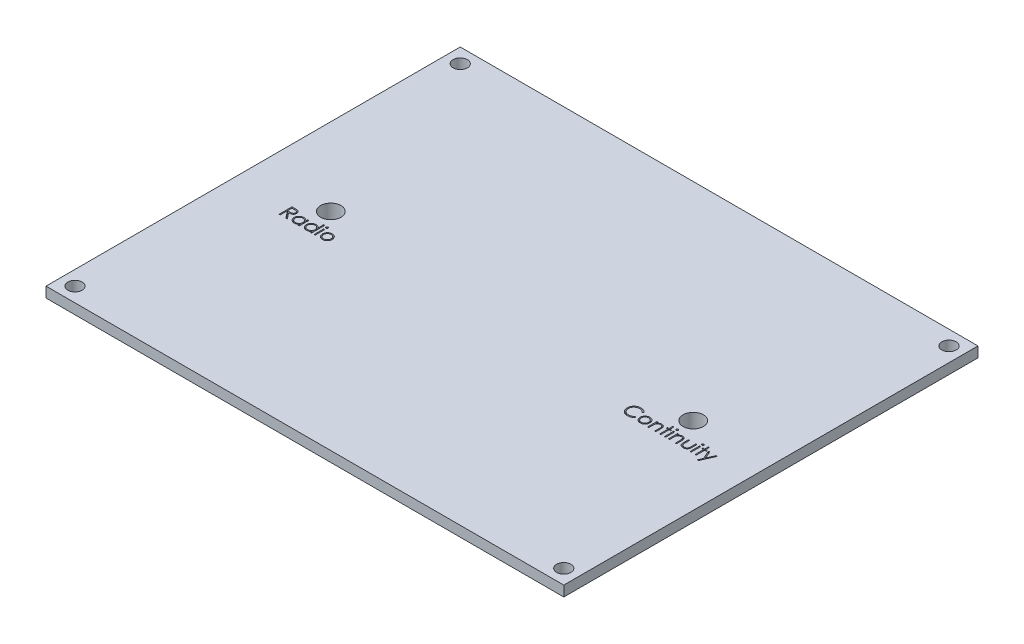
SolidWorks part; units mm, degrees
ref_plane "Front Plane" through (0, 0, 0) normal (0, 0, 1) x (1, 0, 0)
ref_plane "Top Plane" through (0, 0, 0) normal (0, 1, 0) x (1, 0, 0)
ref_plane "Right Plane" through (0, 0, 0) normal (1, 0, 0) x (0, 0, -1)
sketch "Çizim1" plane through (0, 0, 0) normal (0, 1, 0) x (1, 0, 0)
  line L1 (-63.5, 50.8) -> (63.5, 50.8)
  line L2 (-63.5, 50.8) -> (-63.5, -50.8)
  line L3 (-63.5, -50.8) -> (63.5, -50.8)
  line L4 (63.5, 50.8) -> (63.5, -50.8)
  line L5 (-63.5, 50.8) -> (63.5, -50.8) construction
  line L6 (-63.5, -50.8) -> (63.5, 50.8) construction
  point P0 (0, 0)
  dimension "D1" = 127
  dimension "D2" = 101.6
extrude "Yükseklik-Ekstrüzyon1" add sketch "Çizim1" along normal blind 2.54
sketch "Çizim3" plane through (0, 0, 0) normal (0, -1, 0) x (1, 0, 0)
  line L1 (-56.515, 43.815) -> (56.515, 43.815)
  line L2 (-56.515, 43.815) -> (-56.515, -43.815)
  line L3 (-56.515, -43.815) -> (56.515, -43.815)
  line L4 (56.515, 43.815) -> (56.515, -43.815)
  line L5 (-56.515, 43.815) -> (56.515, -43.815) construction
  line L6 (-56.515, -43.815) -> (56.515, 43.815) construction
  point P0 (0, 0)
  dimension "D1" = 113.03
  dimension "D2" = 87.63
extrude "Yükseklik-Ekstrüzyon2" add sketch "Çizim3" along normal blind 1.27 contours L1 L4 L3 L2
sketch "Çizim4" plane through (0, 2.54, 0) normal (0, 1, 0) x (1, 0, 0)
  line L0 (63.5, 50.8) -> (-63.5, 50.8) construction
  line L1 (-63.5, 50.8) -> (-63.5, -50.8) construction
  circle A0 centre (-59.944, 47.244) radius 1.7526
  dimension "D1" = 3.556
  dimension "D2" = 3.556
sketch "Çizim5" plane through (0, 2.54, 0) normal (0, 1, 0) x (1, 0, 0)
  line L0 (63.5, 50.8) -> (-63.5, 50.8) construction
  line L1 (63.5, -50.8) -> (63.5, 50.8) construction
  circle A0 centre (59.944, 47.244) radius 1.7526
  dimension "D1" = 3.556
  dimension "D2" = 3.556
extrude "Kes-Ekstrüzyon1" cut sketch "Çizim4" against normal blind 2.54 contours A0
extrude "Kes-Ekstrüzyon2" cut sketch "Çizim5" against normal blind 2.54 contours A0
sketch "Çizim7" plane through (0, 2.54, 0) normal (0, 1, 0) x (1, 0, 0)
  line L0 (-63.5, 50.8) -> (-63.5, -50.8) construction
  line L1 (-63.5, -50.8) -> (63.5, -50.8) construction
  circle A0 centre (-59.944, -47.244) radius 1.7526
  dimension "D1" = 3.556
  dimension "D2" = 3.556
extrude "Kes-Ekstrüzyon3" cut sketch "Çizim7" against normal blind 2.54
sketch "Çizim9" plane through (0, 2.54, 0) normal (0, 1, 0) x (1, 0, 0)
  line L0 (63.5, -50.8) -> (63.5, 50.8) construction
  line L1 (-63.5, -50.8) -> (63.5, -50.8) construction
  circle A0 centre (59.944, -47.244) radius 1.7526
  dimension "D1" = 3.556
  dimension "D2" = 3.556
extrude "Kes-Ekstrüzyon4" cut sketch "Çizim9" against normal blind 2.54
sketch "Çizim10" plane through (0, 2.54, 0) normal (0, 1, 0) x (1, 0, 0)
  line L1 (-63.5, 50.8) -> (-63.5, -50.8) construction
  circle A1 centre (-44.45, 0) radius 2.5
  dimension "D1" = 19.05
extrude "Kes-Ekstrüzyon5" cut sketch "Çizim10" against normal blind 3.81
sketch "Çizim11" plane through (0, 2.54, 0) normal (0, 1, 0) x (1, 0, 0)
  line L0 (63.5, -50.8) -> (63.5, 50.8) construction
  circle A0 centre (44.45, 0) radius 2.5
  dimension "D1" = 0
  dimension "D2" = 19.05
extrude "Kes-Ekstrüzyon6" cut sketch "Çizim11" against normal blind 3.81 contours A0
sketch "Çizim12" plane through (0, 2.54, 0) normal (0, 1, 0) x (1, 0, 0)
  text T0 "Radio\r\n"
  point P1 (0, 0)
  point P2 (0, 0)
  point P3 (-49.034, -13.8093)
  point P4 (-50.842, -6.5774)
  point P5 (0, 0)
  point P6 (-50.5927, -6.9514)
sketch "Çizim13" plane through (0, 2.54, 0) normal (0, 1, 0) x (1, 0, 0)
  text T0 "Continuity"
  point P1 (34.6948, -6.328)
  point P2 (0, 0)
  point P3 (0, 0)
  point P4 (33.1362, -6.8891)
  point P5 (33.1985, -8.3854)
  dimension "D1" = 0
  dimension "D2" = 83.9782
extrude "Kes-Ekstrüzyon9" cut sketch "Çizim12" against normal blind 0.762
extrude "Kes-Ekstrüzyon10" cut sketch "Çizim13" against normal blind 0.762
